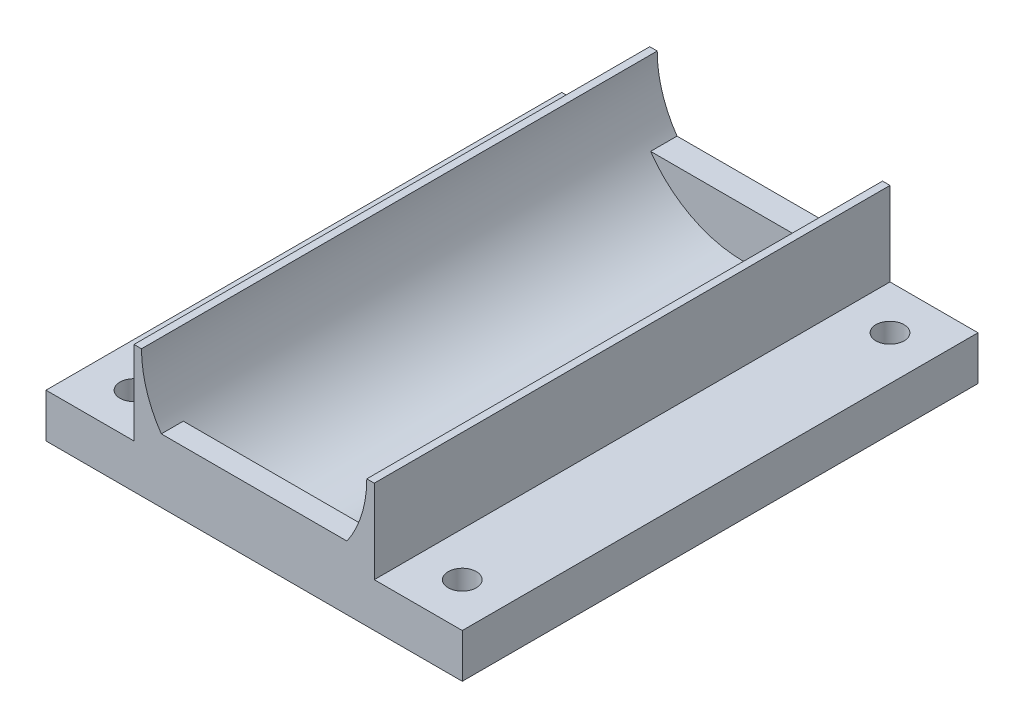
SolidWorks part; units mm, degrees
ref_plane "Спереди" through (0, 0, 0) normal (0, 0, 1) x (1, 0, 0)
ref_plane "Сверху" through (0, 0, 0) normal (0, 1, 0) x (1, 0, 0)
ref_plane "Справа" through (0, 0, 0) normal (1, 0, 0) x (0, 0, -1)
sketch "Эскиз1" plane through (0, 0, 0) normal (0, 1, 0) x (1, 0, 0)
  line L0 (0, 0) -> (27.3, 0)
  line L1 (27.3, 0) -> (27.3, 58.6)
  line L4 (0, 0) -> (0, 58.6)
  line L5 (0, 58.6) -> (27.3, 58.6)
  line L6 (27.3, 0) -> (37.3, 0)
  line L7 (37.3, 58.6) -> (27.3, 58.6)
  line L8 (37.3, 58.6) -> (37.3, 0)
  line L9 (13.65, 58.6) -> (13.65, 0) construction
  line L10 (37.3, 29.3) -> (0, 29.3) construction
  line L11 (-10, 58.6) -> (-10, 0)
  line L12 (-10, 58.6) -> (0, 58.6)
  line L13 (-10, 0) -> (0, 0)
  circle A0 centre (32.3, 53.6) radius 1.6
  circle A1 centre (32.3, 5) radius 1.6
  circle A2 centre (-5, 5) radius 1.6
  circle A3 centre (-5, 53.6) radius 1.6
  dimension "D4" = 5
  dimension "D6" = 3.2
  dimension "D1" = 58.6
  dimension "D2" = 27.3
  dimension "D3" = 10
  dimension "D5" = 5
ref_plane "Плоскость4" through (0, 14.5, 0) normal (0, 1, 0) x (1, 0, 0)
extrude "Бобышка-Вытянуть1" add sketch "Эскиз1" along normal blind 14.5 contours L5 L4 L0 L1 region at (13.65, 0, -29.3)
sketch "Эскиз3" plane through (0, 0, 0) normal (0, 0, 1) x (1, 0, 0)
  line L0 (0, 0) -> (0, 14.5)
  line L1 (0, 14.5) -> (27.3, 14.5)
  line L2 (27.3, 14.5) -> (27.3, 0)
  circle A0 centre (13.65, 14.5) radius 12.8
  dimension "D1" = 25.6
extrude "Вырез-Вытянуть1" cut sketch "Эскиз3" against normal through all contours A0
sketch "Эскиз7" plane through (0, 0, -58.6) normal (0, 0, -1) x (-1, 0, 0)
  line L0 (-27.3, 7.25) -> (0, 7.25)
  line L1 (-27.3, 14.5) -> (-27.3, 0) construction
  line L2 (0, 14.5) -> (0, 0) construction
  line L8 (-26.45, 14.5) -> (-27.3, 14.5)
  line L9 (-27.3, 14.5) -> (-27.3, 0)
  line L10 (-27.3, 0) -> (0, 0)
  line L11 (0, 0) -> (0, 14.5)
  line L12 (0, 14.5) -> (-0.85, 14.5)
  line L14 (-27.3, 7.25) -> (-27.3, 0)
  line L15 (-27.3, 0) -> (0, 0)
  line L16 (0, 0) -> (0, 7.25)
  arc A1 (-26.45, 14.5) -> (-0.85, 14.5) centre (-13.65, 14.5) ccw
  dimension "D1" = 0
extrude "Бобышка-Вытянуть2" add sketch "Эскиз7" against normal blind 3
extrude "Бобышка-Вытянуть3" add sketch "Эскиз7<2>" against normal blind 2.5 from offset 56.1 offset against normal yes
sketch "Эскиз7<2>" plane through (0, 0, -58.6) normal (0, 0, -1) x (-1, 0, 0) same geometry as "Эскиз7"
extrude "Бобышка-Вытянуть4" add sketch "Эскиз1<3>" along normal blind 5 contours L8 L7 L1 L6 A0 A1 | L11 L13 L4 L12 A2 A3 region at (-5, 0, -29.3) region at (32.3, 0, -29.3)
sketch "Эскиз1<3>" plane through (0, 0, 0) normal (0, 1, 0) x (1, 0, 0) same geometry as "Эскиз1"
ref_plane "Plane1" through (24.1988, 7.25, -55.6) normal (0, 0, 1) x (1, 0, 0)
